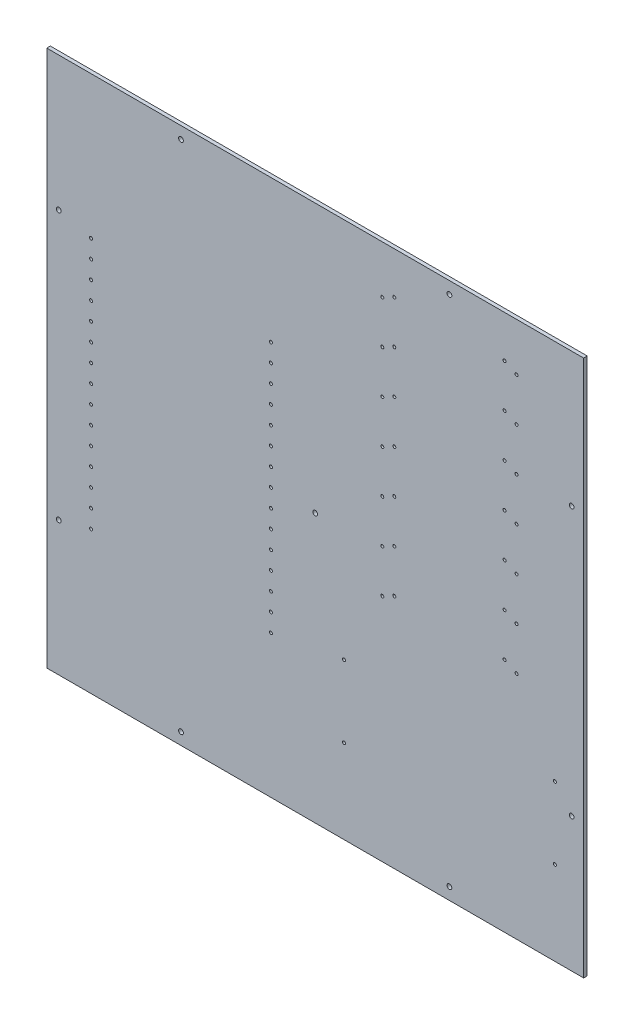
SolidWorks part; units mm, degrees
material "6061-T6 (SS)"
ref_plane "Piano frontale" through (0, 0, 0) normal (0, 0, 1) x (1, 0, 0)
ref_plane "Piano superiore" through (0, 0, 0) normal (0, 1, 0) x (1, 0, 0)
ref_plane "Piano destro" through (0, 0, 0) normal (1, 0, 0) x (0, 0, -1)
sketch "Schizzo1" plane through (0, 0, 0) normal (0, 0, 1) x (1, 0, 0)
  line L0 (10, 448) -> (10, -28.2593) construction
  line L1 (0, 0) -> (448, 0)
  line L2 (0, 0) -> (0, 448)
  line L3 (0, 448) -> (448, 448)
  line L4 (448, 0) -> (448, 448)
  line L5 (0, 224) -> (448, 224) construction
  line L6 (224, 448) -> (224, 0) construction
  line L7 (438, 448) -> (438, -28.2593) construction
  line L8 (0, 438) -> (525.0128, 438) construction
  line L9 (0, 10) -> (525.0128, 10) construction
  line L10 (0, 448) -> (0, 224) construction
  line L11 (0, 448) -> (0, 224) construction
  line L15 (0, 336) -> (224, 336) construction
  line L25 (112, 448) -> (112, 224) construction
  line L38 (36.9588, 287.1268) -> (36.9588, 448) construction
  line L39 (290, 454.3859) -> (290, -79.8136) construction
  line L40 (382, 454.3859) -> (382, -79.8136) construction
  line L41 (280, 457.4164) -> (280, -41.798) construction
  line L42 (392, 457.4164) -> (392, -41.798) construction
  line L43 (204.2813, 100) -> (482.2381, 100) construction
  line L44 (183.4892, 70) -> (499.6284, 70) construction
  line L45 (248, -38.4576) -> (248, 170.1585) construction
  line L46 (183.4892, 130) -> (499.6284, 130) construction
  line L47 (424, -38.4576) -> (424, 170.1585) construction
  line L58 (336, 27.7675) -> (336, 161.4481) construction
  line L65 (224, 224) -> (448, 224) construction
  circle A0 centre (10, 336) radius 2
  circle A1 centre (336, 438) radius 2
  circle A2 centre (438, 336) radius 2
  circle A3 centre (438, 112) radius 2
  circle A4 centre (336, 10) radius 2
  circle A5 centre (112, 10) radius 2
  circle A6 centre (10, 112) radius 2
  circle A7 centre (36.9588, 224) radius 1.25
  circle A8 centre (112, 438) radius 2
  circle A9 centre (36.9588, 239) radius 1.25
  circle A10 centre (36.9588, 254) radius 1.25
  circle A11 centre (36.9588, 269) radius 1.25
  circle A12 centre (36.9588, 284) radius 1.25
  circle A13 centre (36.9588, 299) radius 1.25
  circle A14 centre (36.9588, 314) radius 1.25
  circle A15 centre (36.9588, 329) radius 1.25
  circle A16 centre (248, 70) radius 1.25
  circle A17 centre (248, 130) radius 1.25
  circle A18 centre (424, 130) radius 1.25
  circle A19 centre (424, 70) radius 1.25
  circle A20 centre (290, 413) radius 1.25
  circle A21 centre (280, 408) radius 1.25
  circle A22 centre (392, 408) radius 1.25
  circle A23 centre (382, 413) radius 1.25
  circle A24 centre (290, 377) radius 1.25
  circle A25 centre (280, 372) radius 1.25
  circle A26 centre (392, 372) radius 1.25
  circle A27 centre (382, 377) radius 1.25
  circle A28 centre (290, 341) radius 1.25
  circle A29 centre (280, 336) radius 1.25
  circle A30 centre (392, 336) radius 1.25
  circle A31 centre (382, 341) radius 1.25
  circle A32 centre (290, 305) radius 1.25
  circle A33 centre (280, 300) radius 1.25
  circle A34 centre (392, 300) radius 1.25
  circle A35 centre (382, 305) radius 1.25
  circle A36 centre (290, 269) radius 1.25
  circle A37 centre (280, 264) radius 1.25
  circle A38 centre (392, 264) radius 1.25
  circle A39 centre (382, 269) radius 1.25
  circle A40 centre (290, 233) radius 1.25
  circle A41 centre (280, 228) radius 1.25
  circle A42 centre (392, 228) radius 1.25
  circle A43 centre (382, 233) radius 1.25
  circle A44 centre (290, 197) radius 1.25
  circle A45 centre (280, 192) radius 1.25
  circle A46 centre (392, 192) radius 1.25
  circle A47 centre (382, 197) radius 1.25
  circle A48 centre (36.9588, 119) radius 1.25
  circle A49 centre (36.9588, 134) radius 1.25
  circle A50 centre (36.9588, 149) radius 1.25
  circle A51 centre (36.9588, 164) radius 1.25
  circle A52 centre (36.9588, 179) radius 1.25
  circle A53 centre (36.9588, 194) radius 1.25
  circle A54 centre (36.9588, 209) radius 1.25
  circle A55 centre (187.0412, 209) radius 1.25
  circle A56 centre (187.0412, 194) radius 1.25
  circle A57 centre (187.0412, 179) radius 1.25
  circle A58 centre (187.0412, 164) radius 1.25
  circle A59 centre (187.0412, 149) radius 1.25
  circle A60 centre (187.0412, 134) radius 1.25
  circle A61 centre (187.0412, 119) radius 1.25
  circle A62 centre (187.0412, 329) radius 1.25
  circle A63 centre (187.0412, 314) radius 1.25
  circle A64 centre (187.0412, 299) radius 1.25
  circle A65 centre (187.0412, 284) radius 1.25
  circle A66 centre (187.0412, 269) radius 1.25
  circle A67 centre (187.0412, 254) radius 1.25
  circle A68 centre (187.0412, 239) radius 1.25
  circle A69 centre (187.0412, 224) radius 1.25
  circle A70 centre (224, 224) radius 2
  point P33 (36.9588, 224)
  point P49 (112, 438)
  point P82 (253.9707, 256)
  point P89 (253.9707, 224)
  point P96 (253.9707, 192)
  point P103 (253.9707, 384)
  point P110 (253.9707, 352)
  point P117 (253.9707, 320)
  point P141 (253.9707, 288)
  point P148 (253.9707, 160)
  point P155 (253.9707, 128)
  point P162 (253.9707, 96)
  point P169 (253.9707, 64)
  point P179 (280.1758, 232.4048)
  point P193 (280.1085, 282.4047)
  point P207 (280.0413, 332.4047)
  dimension "D5" = 30
  dimension "D14" = 100
  dimension "D18" = 7
  dimension "D16" = 2.5
  dimension "D17" = 2.5
  dimension "D9" = 4
  dimension "D10" = 2.5
  dimension "D20" = 4
  dimension "D1" = 448
  dimension "D2" = 448
  dimension "D3" = 10
  dimension "D4" = 10
  dimension "D6" = 25
  dimension "D7" = 112
  dimension "D8" = 112
  dimension "D11" = 46
  dimension "D12" = 56
  dimension "D13" = 30
  dimension "D15" = 88
  dimension "D19" = 8
extrude "Estrusione-Estrusione1" add sketch "Schizzo1" against normal blind 3
